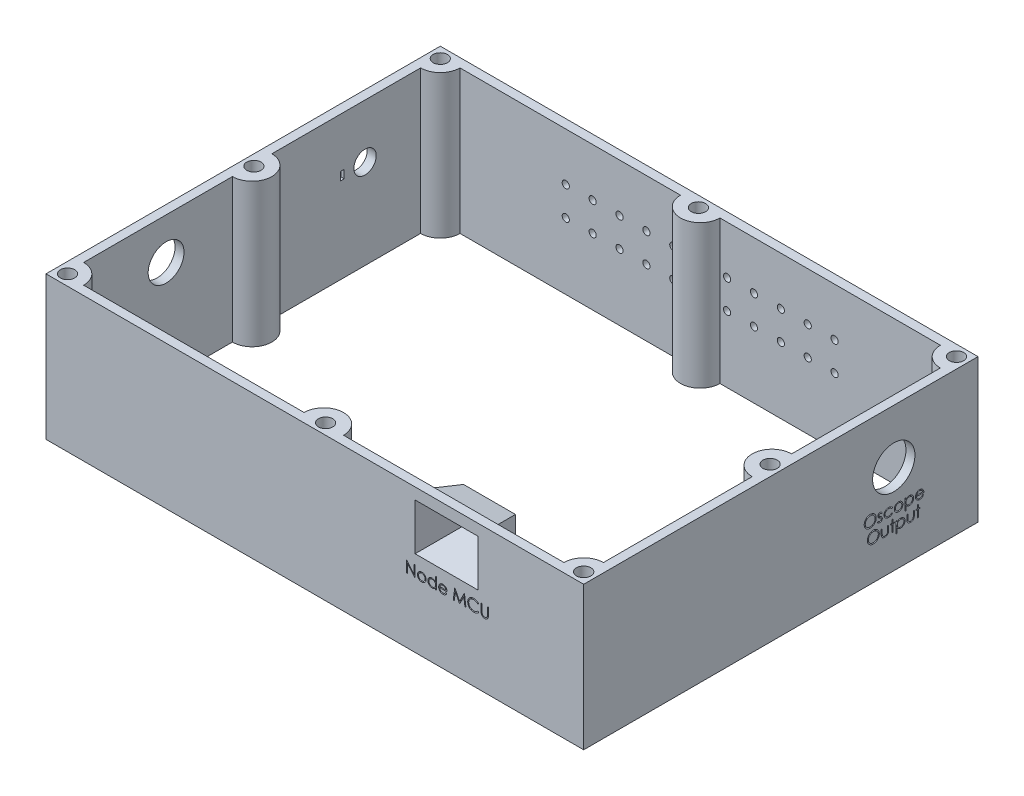
SolidWorks part; units mm, degrees
ref_plane "Front Plane" through (0, 0, 0) normal (0, 0, 1) x (1, 0, 0)
ref_plane "Top Plane" through (0, 0, 0) normal (0, 1, 0) x (1, 0, 0)
ref_plane "Right Plane" through (0, 0, 0) normal (1, 0, 0) x (0, 0, -1)
sketch "Sketch1" plane through (0, 0, 0) normal (0, 1, 0) x (1, 0, 0)
  line L1 (-75, 55) -> (75, 55)
  line L2 (-75, 55) -> (-75, -55)
  line L3 (-75, -55) -> (75, -55)
  line L4 (75, 55) -> (75, -55)
  line L5 (-75, 55) -> (75, -55) construction
  line L6 (-75, -55) -> (75, 55) construction
  line L7 (-72.5, 52.5) -> (72.5, 52.5)
  line L8 (-72.5, 52.5) -> (-72.5, -52.5)
  line L9 (-72.5, -52.5) -> (72.5, -52.5)
  line L10 (72.5, 52.5) -> (72.5, -52.5)
  line L11 (-72.5, 52.5) -> (72.5, -52.5) construction
  line L12 (-72.5, -52.5) -> (72.5, 52.5) construction
  point P0 (0, 0)
  point P6 (0, 0)
  dimension "D1" = 110
  dimension "D2" = 150
  dimension "D3" = 2.5
  dimension "D4" = 2.5
extrude "Wall" add sketch "Sketch1" along normal blind 40
sketch "Sketch2" plane through (0, 0, 0) normal (0, -1, 0) x (1, 0, 0)
  line L0 (-72.5, 52.5) -> (-67, 52.5)
  line L1 (-72.5, 52.5) -> (72.5, 52.5) construction
  line L2 (-72.5, 52.5) -> (-72.5, 47)
  line L3 (-72.5, -52.5) -> (-72.5, 52.5) construction
  line L6 (-72.5, -52.5) -> (-67, -52.5)
  line L7 (72.5, -52.5) -> (-72.5, -52.5) construction
  line L8 (-72.5, -47) -> (-72.5, -52.5)
  line L12 (72.5, -52.5) -> (72.5, -47)
  line L13 (72.5, 52.5) -> (72.5, -52.5) construction
  line L14 (67, -52.5) -> (72.5, -52.5)
  line L17 (72.5, 52.5) -> (67, 52.5)
  line L18 (72.5, 47) -> (72.5, 52.5)
  line L20 (-5.5, 52.5) -> (5.5, 52.5)
  line L21 (75, 55) -> (75, -55) construction
  line L22 (-72.5, -5.5) -> (-72.5, 5.5)
  line L23 (75, -55) -> (-75, -55) construction
  line L24 (-5.5, -52.5) -> (5.5, -52.5)
  line L26 (72.5, -5.5) -> (72.5, 5.5)
  arc A0 (-67, 52.5) -> (-72.5, 47) centre (-72.5, 52.5) cw
  arc A2 (-67, -52.5) -> (-72.5, -47) centre (-72.5, -52.5) ccw
  arc A4 (72.5, -47) -> (67, -52.5) centre (72.5, -52.5) ccw
  arc A6 (67, 52.5) -> (72.5, 47) centre (72.5, 52.5) ccw
  arc A8 (5.5, 52.5) -> (-5.5, 52.5) centre (0, 52.5) cw
  arc A9 (-72.5, 5.5) -> (-72.5, -5.5) centre (-72.5, 0) cw
  arc A10 (5.5, -52.5) -> (-5.5, -52.5) centre (0, -52.5) ccw
  arc A11 (72.5, 5.5) -> (72.5, -5.5) centre (72.5, 0) ccw
  point P12 (0, 52.5)
  point P25 (-72.5, 0)
  point P43 (0, -52.5)
  point P47 (72.5, 0)
  dimension "D3" = 5.5
  dimension "D4" = 11
  dimension "D1" = 5.5
  dimension "D2" = 5.5
  dimension "D5" = 75
  dimension "D6" = 11
  dimension "D7" = 5.5
  dimension "D8" = 5.5
  dimension "D9" = 55
  dimension "D10" = 11
  dimension "D11" = 5.5
  dimension "D12" = 5.5
  dimension "D13" = 75
  dimension "D14" = 11
  dimension "D15" = 5.5
  dimension "D16" = 5.5
  dimension "D17" = 55
extrude "Boss-Extrude3" add sketch "Sketch2" against normal blind 40
sketch "Sketch4" plane through (0, 0, 0) normal (0, -1, 0) x (1, 0, 0)
  line L0 (-75, 55) -> (75, 55) construction
  line L1 (-75, -55) -> (-75, 55) construction
  line L3 (75, 55) -> (75, -55) construction
  line L4 (75, -55) -> (-75, -55) construction
  circle A0 centre (-72, 0) radius 2
  circle A1 centre (-72, -52) radius 2
  circle A2 centre (0, -52) radius 2
  circle A3 centre (72, 0) radius 2
  circle A4 centre (72, -52) radius 2
  circle A5 centre (72, 52) radius 2
  circle A6 centre (0, 52) radius 2
  circle A7 centre (-72, 52) radius 2
  dimension "D1" = 4
  dimension "D4" = 4
  dimension "D7" = 4
  dimension "D10" = 4
  dimension "D13" = 4
  dimension "D18" = 4
  dimension "D19" = 4
  dimension "D23" = 4
  dimension "D2" = 3
  dimension "D3" = 3
  dimension "D5" = 3
  dimension "D6" = 75
  dimension "D8" = 3
  dimension "D9" = 3
  dimension "D11" = 3
  dimension "D12" = 55
  dimension "D14" = 3
  dimension "D15" = 3
  dimension "D16" = 3
  dimension "D17" = 75
  dimension "D20" = 3
  dimension "D21" = 3
  dimension "D22" = 3
  dimension "D24" = 55
extrude "Connector bottom" cut sketch "Sketch4" against normal blind 5
sketch "Sketch6" plane through (0, 40, 0) normal (0, 1, 0) x (1, 0, 0)
  line L0 (75, 55) -> (-75, 55) construction
  line L1 (-75, 55) -> (-75, -55) construction
  line L2 (-75, -55) -> (75, -55) construction
  line L3 (75, -55) -> (75, 55) construction
  circle A0 centre (72, 52) radius 2
  circle A1 centre (72, 0) radius 2
  circle A2 centre (72, -52) radius 2
  circle A3 centre (0, -52) radius 2
  circle A4 centre (-72, -52) radius 2
  circle A5 centre (-72, 0) radius 2
  circle A6 centre (-72, 52) radius 2
  circle A7 centre (0, 52) radius 2
  point P22 (0, -55)
  dimension "D1" = 4
  dimension "D4" = 4
  dimension "D8" = 4
  dimension "D12" = 4
  dimension "D13" = 4
  dimension "D18" = 4
  dimension "D19" = 4
  dimension "D24" = 4
  dimension "D2" = 3
  dimension "D3" = 75
  dimension "D5" = 3
  dimension "D6" = 3
  dimension "D7" = 55
  dimension "D9" = 3
  dimension "D10" = 3
  dimension "D11" = 3
  dimension "D14" = 3
  dimension "D15" = 75
  dimension "D16" = 3
  dimension "D17" = 3
  dimension "D20" = 3
  dimension "D21" = 55
  dimension "D22" = 3
  dimension "D23" = 3
extrude "Connector top" cut sketch "Sketch6" against normal blind 5
sketch "Sketch7" plane through (0, 0, 55) normal (0, 0, 1) x (1, 0, 0)
  line L0 (43.97, 30.54) -> (33.97, 30.54) construction
  line L1 (33.97, 30.54) -> (33.97, 37.04) construction
  line L2 (33.97, 37.04) -> (43.97, 37.04) construction
  line L3 (43.97, 37.04) -> (43.97, 30.54) construction
  line L4 (-75, 0) -> (75, 0) construction
  line L5 (75, 40) -> (75, 0) construction
  dimension "D1" = 30.54
  dimension "D2" = 6.5
  dimension "D3" = 10
  dimension "D4" = 31.03
ref_plane "Plane2" through (0, 0, 43) normal (0, 0, 1) x (1, 0, 0)
sketch "Sketch9" plane through (0, 0, 43) normal (0, 0, 1) x (1, 0, 0)
  line L0 (-75, 0) -> (75, 0) construction
  line L1 (29.47, 35.355) -> (43.97, 35.355)
  line L2 (29.47, 35.355) -> (29.47, 25.355)
  line L3 (29.47, 25.355) -> (43.97, 25.355)
  line L4 (43.97, 35.355) -> (43.97, 25.355)
  line L5 (29.47, 35.355) -> (43.97, 25.355) construction
  line L6 (29.47, 25.355) -> (43.97, 35.355) construction
  line L7 (75, 40) -> (75, 0) construction
  point P0 (36.72, 30.355)
  dimension "D1" = 30.355
  dimension "D2" = 38.28
  dimension "D3" = 14.5
  dimension "D4" = 10
sketch "Sketch10" plane through (0, 0, 55) normal (0, 0, 1) x (1, 0, 0)
  line L1 (33.97, 37.04) -> (43.97, 37.04)
  line L2 (33.97, 37.04) -> (33.97, 30.54)
  line L3 (33.97, 30.54) -> (43.97, 30.54)
  line L4 (43.97, 37.04) -> (43.97, 30.54)
  line L5 (33.97, 37.04) -> (43.97, 30.54) construction
  line L6 (33.97, 30.54) -> (43.97, 37.04) construction
  point P0 (38.97, 33.79)
sketch "Sketch11" plane through (0, 0, 55) normal (0, 0, 1) x (1, 0, 0)
  line L0 (29.47, 25.355) -> (43.97, 25.355) construction
  line L1 (26.47, 38.355) -> (46.97, 38.355)
  line L2 (26.47, 38.355) -> (26.47, 22.355)
  line L3 (26.47, 22.355) -> (46.97, 22.355)
  line L4 (46.97, 38.355) -> (46.97, 22.355)
  line L5 (43.97, 35.355) -> (43.97, 25.355) construction
  line L6 (29.47, 35.355) -> (43.97, 35.355) construction
  line L7 (29.47, 35.355) -> (29.47, 25.355) construction
  dimension "D1" = 3
  dimension "D2" = 3
  dimension "D3" = 3
  dimension "D4" = 3
ref_plane "Plane3" through (31.2659, 0, -7.8165) normal (0.9701, 0, -0.2425) x (-0.2425, 0, -0.9701)
sketch "Sketch12" plane through (31.2659, 0, -7.8165) normal (0.9701, 0, -0.2425) x (-0.2425, 0, -0.9701)
  line L0 (-64.7497, 22.355) -> (-52.3804, 25.355) construction
  line L1 (-64.7497, 38.355) -> (-52.3804, 35.355) construction
ref_plane "Plane4" through (37.8541, 0, 9.4635) normal (-0.9701, 0, -0.2425) x (-0.2425, 0, 0.9701)
sketch "Sketch13" plane through (37.8541, 0, 9.4635) normal (-0.9701, 0, -0.2425) x (-0.2425, 0, 0.9701)
  line L0 (46.9379, 22.355) -> (34.5686, 25.355) construction
  line L1 (34.5686, 35.355) -> (46.9379, 38.355) construction
sketch "Sketch14" plane through (0, 0, 55) normal (0, 0, 1) x (1, 0, 0)
  line L0 (26.47, 38.355) -> (46.97, 38.355) construction
  line L1 (27.97, 36.855) -> (45.47, 36.855)
  line L2 (27.97, 36.855) -> (27.97, 23.855)
  line L3 (27.97, 23.855) -> (45.47, 23.855)
  line L4 (45.47, 36.855) -> (45.47, 23.855)
  line L5 (46.97, 38.355) -> (46.97, 22.355) construction
  line L6 (26.47, 22.355) -> (46.97, 22.355) construction
  line L7 (26.47, 38.355) -> (26.47, 22.355) construction
  dimension "D1" = 1.5
  dimension "D2" = 1.5
  dimension "D3" = 1.5
  dimension "D4" = 1.5
loft "Loft2" add profiles "Sketch11", "Sketch9"
ref_plane "Plane5" through (34.3089, 0, 4.2886) normal (0.9923, 0, 0.124) x (0.124, 0, -0.9923)
sketch "Sketch15" plane through (34.3089, 0, 4.2886) normal (0.9923, 0, 0.124) x (0.124, 0, -0.9923)
  line L0 (-51.106, 23.855) -> (-39.0126, 25.355) construction
  line L1 (-51.106, 36.855) -> (-39.0126, 35.355) construction
ref_plane "Plane6" through (38.0012, 0, -4.7502) normal (0.9923, 0, -0.124) x (-0.124, 0, -0.9923)
sketch "Sketch16" plane through (38.0012, 0, -4.7502) normal (0.9923, 0, -0.124) x (-0.124, 0, -0.9923)
  line L0 (-60.2151, 23.855) -> (-48.1218, 25.355) construction
  line L1 (-60.2151, 36.855) -> (-48.1218, 35.355) construction
sketch "Sketch17" plane through (0, 0, 55) normal (0, 0, 1) x (1, 0, 0)
  line L0 (25.139, 18) -> (48.301, 18) construction
  line L1 (-75, 0) -> (75, 0) construction
  line L2 (29.47, 25.355) -> (43.97, 25.355) construction
  text T0 "Node MCU\r\n"
  point P6 (36.72, 18)
  point P9 (36.72, 25.355)
  dimension "D1" = 18
sketch "Sketch18" plane through (0, 0, 43) normal (0, 0, -1) x (-1, 0, 0)
  line L0 (-29.47, 35.355) -> (-43.97, 35.355) construction
  line L1 (-30.97, 26.855) -> (-42.47, 26.855)
  line L2 (-30.97, 26.855) -> (-30.97, 33.855)
  line L3 (-30.97, 33.855) -> (-42.47, 33.855)
  line L4 (-42.47, 26.855) -> (-42.47, 33.855)
  line L5 (-43.97, 35.355) -> (-43.97, 25.355) construction
  line L6 (-29.47, 25.355) -> (-43.97, 25.355) construction
  line L7 (-29.47, 35.355) -> (-29.47, 25.355) construction
  dimension "D1" = 1.5
  dimension "D2" = 1.5
  dimension "D3" = 1.5
  dimension "D4" = 1.5
  dimension "D5" = 7
  dimension "D6" = 11.5
loft "Cut-Loft1" cut profiles "Sketch18", "Sketch14"
sketch "Sketch19" plane through (75, 0, 0) normal (1, 0, 0) x (0, 0, -1)
  line L0 (55, 40) -> (55, 0) construction
  line L1 (-55, 40) -> (55, 40) construction
  circle A0 centre (31.5, 25) radius 5.9
  dimension "D1" = 11.8
  dimension "D2" = 23.5
  dimension "D3" = 15
extrude "Oscope" cut sketch "Sketch19" against normal blind 5
hole_wizard "Tap Drill for M6 Helicoil1" positions "3DSketch1" profile "Sketch21" hole size "M6x1.0" standard "ANSI Metric"
sketch3d "3DSketch1"
  line L0 (-75, 40, -55) -> (-75, 0, -55) construction
  line L1 (-75, 40, -55) -> (-75, 40, 55) construction
  point P0 (-75, 25, -31.5)
  dimension "D1" = 23.5
  dimension "D2" = 15
sketch "Sketch21" plane through (-75, 25, -31.5) normal (0, 1, 0) x (0, 0, 1)
  line L0 (0, 0) -> (0, 6.8777)
  line L1 (0, 6.8777) -> (3.125, 5)
  line L2 (3.125, 5) -> (3.125, 0)
  line L5 (3.125, 0) -> (0, 0)
  line L10 (0, 6.8777) -> (-3.125, 5) construction
  line L11 (0, -6.35) -> (0, 107.95) construction
  dimension "Hole Dia." = 6.25
  dimension "Hole Depth" = 5
  dimension "Drill Angle" = 118
sketch "Sketch23" plane through (-72.5, 0, 0) normal (1, 0, 0) x (0, 0, -1)
  line L3 (25.7, 26.15) -> (24.6, 26.15)
  line L4 (25.7, 26.15) -> (25.7, 23.85)
  line L5 (25.7, 23.85) -> (24.6, 23.85)
  line L6 (24.6, 26.15) -> (24.6, 23.85)
  line L7 (25.7, 26.15) -> (24.6, 23.85) construction
  line L8 (25.7, 23.85) -> (24.6, 26.15) construction
  point P0 (25.15, 25)
  dimension "D1" = 2.3
  dimension "D2" = 1.1
  dimension "D3" = 5.8
extrude "Cut-Extrude3" cut sketch "Sketch23" against normal blind 0.9
sketch "PCB_Input" plane through (-72.5, 0, 0) normal (1, 0, 0) x (0, 0, -1)
  line L0 (-5.5, 40) -> (-47, 40) construction
  line L1 (-52, 35) -> (-32, 35)
  line L2 (-52, 35) -> (-52, 11)
  line L3 (-52, 11) -> (-32, 11)
  line L4 (-32, 35) -> (-32, 11)
  line L5 (-52, 23) -> (-32, 23) construction
  line L7 (-41.5, 35) -> (-41.5, 32.5) construction
  line L8 (-41.5, 11) -> (-41.5, 13.5) construction
  line L12 (-55, 40) -> (-55, 0) construction
  point P17 (-52, 23)
  dimension "D1" = 20
  dimension "D2" = 24
  dimension "D3" = 5
  dimension "D4" = 2.5
  dimension "D5" = 10.5
  dimension "D6" = 2.5
  dimension "D7" = 10.5
  dimension "D8" = 3
sketch "Sketch31" plane through (75, 0, 0) normal (1, 0, 0) x (0, 0, -1)
  line L0 (23.0129, 13.6431) -> (39.9871, 13.6431) construction
  line L1 (23.8825, 9.4079) -> (39.1175, 9.4079) construction
  text T0 "Oscope"
  text T1 "Output\r\n"
  point P8 (31.5, 13.6431)
  point P9 (31.5, 9.4079)
sketch "Sketch33" plane through (-75, 0, 0) normal (-1, 0, 0) x (0, 0, 1)
  line L0 (-44.8443, 23.3841) -> (-38.028, 23.3841) construction
  line L1 (-38.028, 23.3841) -> (-24.972, 23.3841) construction
  line L2 (-24.972, 23.3841) -> (-18.4688, 23.3841) construction
  text T0 "On"
  text T1 "Off"
  point P10 (-31.5, 23.3841)
sketch "Sketch34" plane through (-75, 0, 0) normal (-1, 0, 0) x (0, 0, 1)
  line L0 (55, 40) -> (55, 0) construction
  line L1 (-55, 0) -> (55, 0) construction
  circle A0 centre (24, 28.5) radius 5
  dimension "D2" = 10
  dimension "D1" = 31
  dimension "D3" = 28.5
extrude "Jack" cut sketch "Sketch34" against normal up to next contours A0
sketch "Sketch35" plane through (-75, 0, 0) normal (-1, 0, 0) x (0, 0, 1)
  line L0 (12.9122, 18.5) -> (35.0878, 18.5) construction
  text T0 "ECG Input"
  point P5 (24, 18.5)
  dimension "D1" = 10
sketch "Sketch36" plane through (0, 0, -55) normal (0, 0, -1) x (-1, 0, 0)
  line L0 (-55.4839, 30) -> (-55.4839, 15) construction
  line L1 (-55.4839, 15) -> (55.4839, 15) construction
  line L2 (55.4839, 15) -> (55.4839, 30) construction
  line L3 (55.4839, 30) -> (-55.4839, 30) construction
  line L4 (-75, 0) -> (75, 0) construction
  circle A0 centre (-37.5, 26.5537) radius 1
  circle A1 centre (-30, 26.5537) radius 1
  circle A2 centre (-22.5, 26.5537) radius 1
  circle A3 centre (-15, 26.5537) radius 1
  circle A4 centre (-7.5, 26.5537) radius 1
  circle A6 centre (7.5, 26.5537) radius 1
  circle A7 centre (15, 26.5537) radius 1
  circle A8 centre (22.5, 26.5537) radius 1
  circle A9 centre (30, 26.5537) radius 1
  circle A10 centre (37.5, 26.5537) radius 1
  circle A11 centre (37.5, 18.5174) radius 1
  circle A12 centre (30, 18.5174) radius 1
  circle A13 centre (22.5, 18.5174) radius 1
  circle A14 centre (15, 18.5174) radius 1
  circle A15 centre (7.5, 18.5174) radius 1
  circle A17 centre (-7.5, 18.5174) radius 1
  circle A18 centre (-15, 18.5174) radius 1
  circle A19 centre (-22.5, 18.5174) radius 1
  circle A20 centre (-30, 18.5174) radius 1
  circle A21 centre (-37.5, 18.5174) radius 1
  point P8 (0, 15)
  dimension "D3" = 2
  dimension "D1" = 15
  dimension "D2" = 15
  dimension "D4" = 7.5
  dimension "D5" = 7.5
  dimension "D6" = 7.5
  dimension "D7" = 7.5
  dimension "D10" = 7.5
  dimension "D11" = 7.5
  dimension "D12" = 7.5
  dimension "D13" = 7.5
extrude "Cut-Extrude4" cut sketch "Sketch36" against normal up to next
extrude "Cut-Extrude5" cut sketch "Sketch35" against normal blind 1.5
extrude "Cut-Extrude6" cut sketch "Sketch33" against normal blind 1.5
extrude "Cut-Extrude7" cut sketch "Sketch17" against normal blind 1.5
extrude "Cut-Extrude8" cut sketch "Sketch31" against normal blind 1.5
